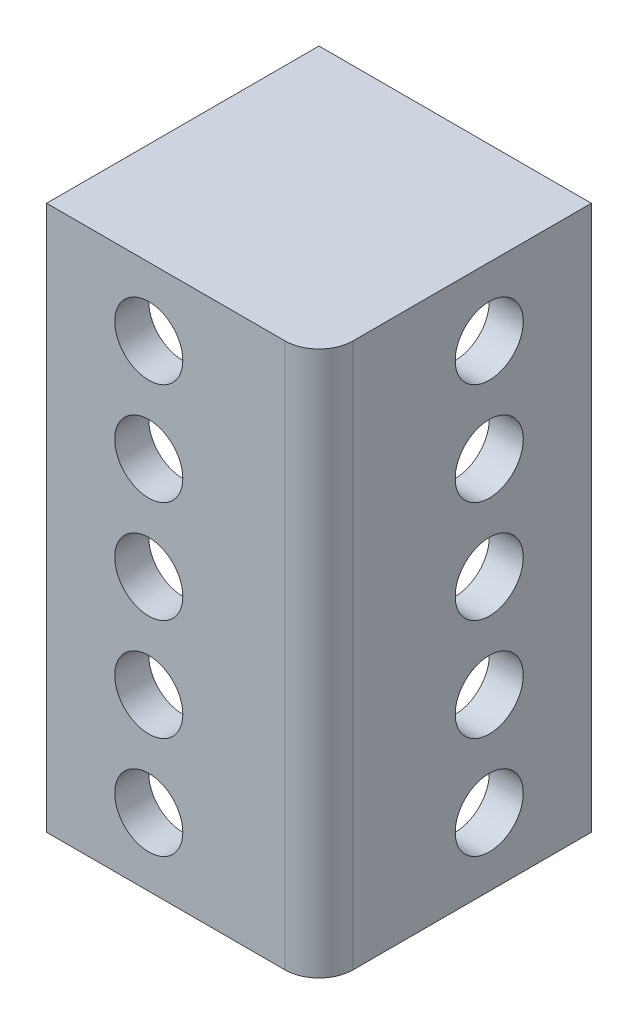
SolidWorks part; units mm, degrees
ref_plane "Front Plane" through (0, 0, 0) normal (0, 0, 1) x (1, 0, 0)
ref_plane "Top Plane" through (0, 0, 0) normal (0, 1, 0) x (1, 0, 0)
ref_plane "Right Plane" through (0, 0, 0) normal (1, 0, 0) x (0, 0, -1)
sketch "Sketch2" plane through (0, 0, 0) normal (0, 1, 0) x (1, 0, 0)
  line L1 (-41.3514, 76.4779) -> (60.2486, 76.4779)
  line L2 (-41.3514, 76.4779) -> (-41.3514, -25.1221)
  line L3 (-41.3514, -25.1221) -> (60.2486, -25.1221)
  line L4 (60.2486, 76.4779) -> (60.2486, -25.1221)
  dimension "D1" = 101.6
  dimension "D2" = 101.6
extrude "Boss-Extrude1" add sketch "Sketch2" along normal blind 203.2
ref_plane "Plane1" through (0, 101.6, 0) normal (0, 1, 0) x (1, 0, 0)
sketch "Sketch4" plane through (0, 101.6, 0) normal (0, 1, 0) x (1, 0, 0)
  line L0 (60.2486, -25.1221) -> (60.2486, 76.4779) construction
  line L1 (-41.3514, 76.4779) -> (47.5486, 76.4779)
  line L2 (-41.3514, 76.4779) -> (-41.3514, -12.4221)
  line L3 (-41.3514, -12.4221) -> (47.5486, -12.4221)
  line L4 (47.5486, 76.4779) -> (47.5486, -12.4221)
  line L5 (-41.3514, -25.1221) -> (60.2486, -25.1221) construction
  dimension "D1" = 12.7
  dimension "D2" = 12.7
extrude "Cut-Extrude1" cut sketch "Sketch4" along normal mid plane 190.5
fillet "Fillet1" radius 12.7 2 edges at (60.2486, 101.6, 25.1221) (47.5486, 101.6, 12.4221)
sketch "Sketch5" plane through (0, 0, 25.1221) normal (0, 0, 1) x (1, 0, 0)
  line L0 (-41.3514, 203.2) -> (47.5486, 203.2) construction
  line L1 (-41.3514, 0) -> (47.5486, 0) construction
  line L2 (-41.3514, 203.2) -> (-41.3514, 0) construction
  circle A0 centre (-3.2514, 177.8) radius 12.7
  circle A1 centre (-3.2514, 139.7) radius 12.7
  circle A2 centre (-3.2514, 101.6) radius 12.7
  circle A3 centre (-3.2514, 63.5) radius 12.7
  circle A4 centre (-3.2514, 25.4) radius 12.7
  dimension "D1" = 25.4
  dimension "D3" = 25.4
  dimension "D4" = 38.1
  dimension "D2" = 5
extrude "Cut-Extrude2" cut sketch "Sketch5" against normal through all
sketch "Sketch6" plane through (60.2486, 0, 0) normal (1, 0, 0) x (0, 0, -1)
  line L0 (-12.4221, 203.2) -> (76.4779, 203.2) construction
  line L1 (76.4779, 203.2) -> (76.4779, 0) construction
  circle A0 centre (38.3779, 177.8) radius 12.7
  circle A1 centre (38.3779, 139.7) radius 12.7
  circle A2 centre (38.3779, 101.6) radius 12.7
  circle A3 centre (38.3779, 63.5) radius 12.7
  circle A4 centre (38.3779, 25.4) radius 12.7
  dimension "D1" = 25.4
  dimension "D2" = 38.1
  dimension "D3" = 5
extrude "Cut-Extrude3" cut sketch "Sketch6" against normal through all
sketch "Sketch7" plane through (0, 6.35, 0) normal (0, 1, 0) x (1, 0, 0)
  line L0 (60.2486, -12.4221) -> (60.2486, 76.4779) construction
  line L1 (-41.3514, 76.4779) -> (47.5486, 76.4779)
  line L2 (-41.3514, 76.4779) -> (-41.3514, -12.4221)
  line L3 (-41.3514, -12.4221) -> (34.8486, -12.4221)
  line L4 (47.5486, 76.4779) -> (47.5486, 0.2779)
  line L5 (-41.3514, -25.1221) -> (47.5486, -25.1221) construction
  arc A0 (34.8486, -12.4221) -> (47.5486, 0.2779) centre (34.8486, 0.2779) ccw
  dimension "D3" = 12.7
  dimension "D1" = 12.7
  dimension "D2" = 12.7
extrude "Cut-Extrude4" cut sketch "Sketch7" against normal through all
